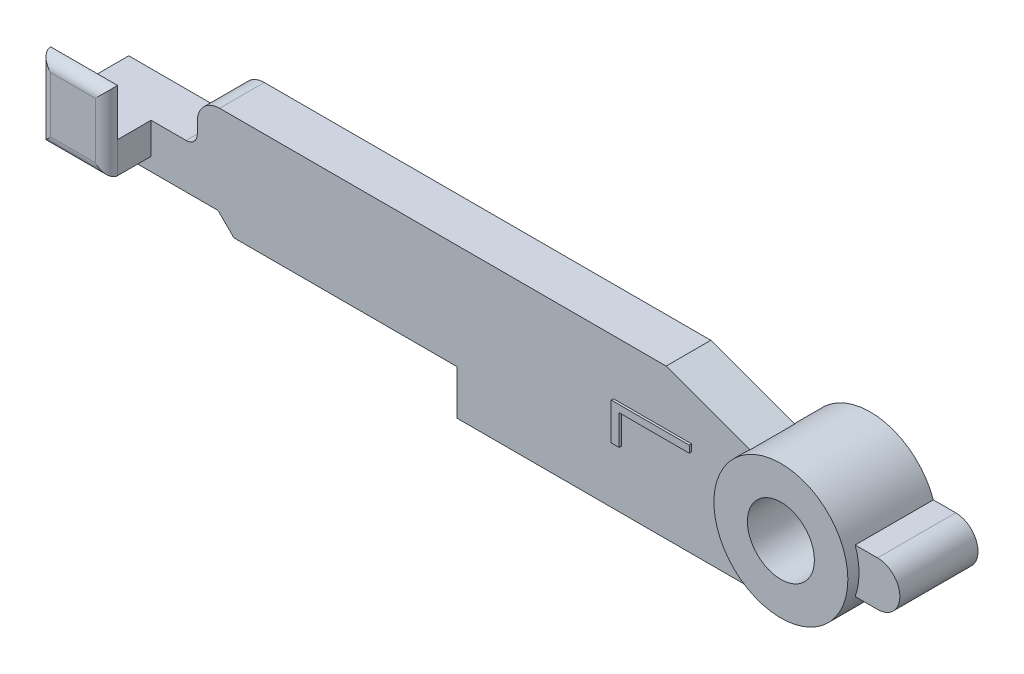
SolidWorks part; units mm, degrees
ref_plane "Piano frontale" through (0, 0, 0) normal (0, 0, 1) x (1, 0, 0)
ref_plane "Piano superiore" through (0, 0, 0) normal (0, 1, 0) x (1, 0, 0)
ref_plane "Piano destro" through (0, 0, 0) normal (1, 0, 0) x (0, 0, -1)
sketch "Schizzo1" plane through (0, 0, 0) normal (0, 0, 1) x (1, 0, 0)
  line L0 (19.0188, 0) -> (-19.0188, 0) construction
  line L1 (0, 0) -> (0, 8.6004) construction
  line L2 (-16.7071, 0.7929) -> (-10.7071, 0.7929)
  line L3 (-10.7071, 0.7929) -> (-10, 1.5)
  line L4 (-10, 1.5) -> (0, 1.5)
  line L5 (0, 1.5) -> (0, 3.5)
  line L6 (0, 3.5) -> (15, 3.5)
  line L7 (15, 3.5) -> (15, 0)
  line L8 (15, 0) -> (15, -1.155)
  line L9 (15, -1.155) -> (9.3618, -3.2071)
  line L10 (9.3618, -3.2071) -> (-11.6382, -3.2071)
  line L11 (-11.6382, -3.2071) -> (-11.6382, -1.2071)
  line L12 (-11.6382, -1.2071) -> (-16.7071, -1.2071)
  line L13 (-16.7071, -1.2071) -> (-16.7071, 0.7929)
  point P4 (0, 0)
  dimension "D1" = 15
  dimension "D2" = 10
  dimension "D3" = 6
  dimension "D4" = 1
  dimension "D5" = 2
  dimension "D6" = 6
  dimension "D7" = 20
  dimension "D8" = 21
  dimension "D9" = 3.5
  dimension "D10" = 45
  dimension "D11" = 2
  dimension "D12" = 2
extrude "Estrusione-Estrusione1" add sketch "Schizzo1" along normal blind 2
fillet "Raccordo1" radius 1 1 edges at (-11.6382, -3.2071, 1)
fillet "Raccordo2" radius 0.5 1 edges at (-11.6382, -1.2071, 1)
sketch "Schizzo2" plane through (0, 0, 0) normal (0, 0, 1) x (1, 0, 0)
  line L0 (-10.7071, 0.7929) -> (22.9117, 0.7929) construction
  line L1 (15, -1.155) -> (15, 3.5) construction
  line L2 (15, 3.5) -> (0, 3.5) construction
  circle A0 centre (15, 0.5) radius 3
  dimension "D1" = 6
extrude "Estrusione-Estrusione2" add sketch "Schizzo2" along direction (0, 0, -1) on the side of the normal blind 2.5 and the other way blind 1.5
sketch "Schizzo3" plane through (0, 0, 0) normal (0, 0, 1) x (1, 0, 0)
  line L0 (15, 0.5) -> (16.6892, 0.5) construction
  line L1 (18.8284, 1.5) -> (17.8284, 1.5)
  line L4 (18.8284, -0.5) -> (17.8284, -0.5)
  line L5 (18.8284, 1.5) -> (18.8284, 0.5) construction
  arc A1 (18.8284, -0.5) -> (18.8284, 1.5) centre (18.8284, 0.5) ccw
  circle A2 centre (15, 0.5) radius 3 construction
  arc A3 (17.8284, -0.5) -> (17.8284, 1.5) centre (15, 0.5) ccw
  dimension "D2" = 1
  dimension "D3" = 1
  dimension "D4" = 1
extrude "Estrusione-Estrusione3" add sketch "Schizzo3" along normal up to surface and the other way up to surface up to face at (-4.9758, -0.1872, 2) other way up to face at (18, 0.5, -1.5)
sketch "Schizzo4" plane through (-16.7071, 0, 0) normal (-1, 0, 0) x (0, 0, 1)
  line L0 (2, -1.2071) -> (3.5, -1.2071)
  line L1 (3.5, -1.2071) -> (3.5, -3.3071)
  line L2 (3.5, -3.3071) -> (4, -3.3071)
  line L3 (4, -3.3071) -> (4, 0.1929)
  line L4 (4, 0.1929) -> (2, 0.1929)
  line L5 (2, 0.7929) -> (2, -1.2071) construction
  line L6 (2, 0.1929) -> (2, -1.2071)
  line L9 (0, 0.7929) -> (0, -1.2071) construction
  dimension "D1" = 1.4
  dimension "D2" = 3.5
  dimension "D3" = 0.5
  dimension "D4" = 4
extrude "Estrusione-Estrusione4" add sketch "Schizzo4" against normal blind 3
fillet "Raccordo3" radius 0.5 4 edges at (-15.2071, 0.1929, 4) (-13.7071, -1.5571, 4) (-15.2071, -3.3071, 4) (-16.7071, -1.5571, 4)
sketch "Schizzo5" plane through (0, 0, 2.5) normal (0, 0, 1) x (1, 0, 0)
  circle A0 centre (15, 0.5) radius 1.5
  circle A1 centre (15, 0.5) radius 3 construction
  dimension "D1" = 1.5
extrude "Taglio-Estrusione1" cut sketch "Schizzo5" against normal through all
mirror "Specchia2" about plane through (0, 0, 0) normal (0, 1, 0) of bodies 105 106
delete or keep bodies "Corpo-Elimina/Mantieni 1" type delete bodies bodies 105
sketch "Schizzo6" plane through (0, 0, 2) normal (0, 0, 1) x (1, 0, 0)
  line L0 (7, 1.2071) -> (7, -3.5) construction
  line L1 (15, -3.5) -> (0, -3.5) construction
  line L2 (0, -3.5) -> (0, -1.5) construction
  line L5 (-10.6382, 3.2071) -> (9.3618, 3.2071) construction
  text T0 "L\r\n"
  point P5 (7, -3.5)
  dimension "D1" = 7
  dimension "D2" = 2
extrude "Estrusione-Estrusione5" add sketch "Schizzo6" along normal blind 0.1
sketch "Schizzo8" plane through (0, 0, 0) normal (0, 0, -1) x (-1, 0, 0)
  line L1 (16.7071, 1.2071) -> (13.7071, 1.2071) construction
  line L2 (16.7071, 1.2071) -> (16.7071, -0.1929) construction
  line L3 (16.7071, -0.1929) -> (13.7071, -0.1929) construction
  line L4 (13.7071, 1.2071) -> (13.7071, -0.1929) construction
  line L5 (16.7071, 1.2071) -> (13.7071, -0.1929) construction
  line L6 (16.7071, -0.1929) -> (13.7071, 1.2071) construction
  line L7 (13.7071, -0.1929) -> (16.7071, -0.1929) construction
  line L8 (13.7071, -0.1929) -> (16.7071, -0.1929)
  point P4 (15.2071, 0.5071)
ref_axis "Assi1" through (-15.2071, 0.5071, 5.921) along (0, 0, -1)
